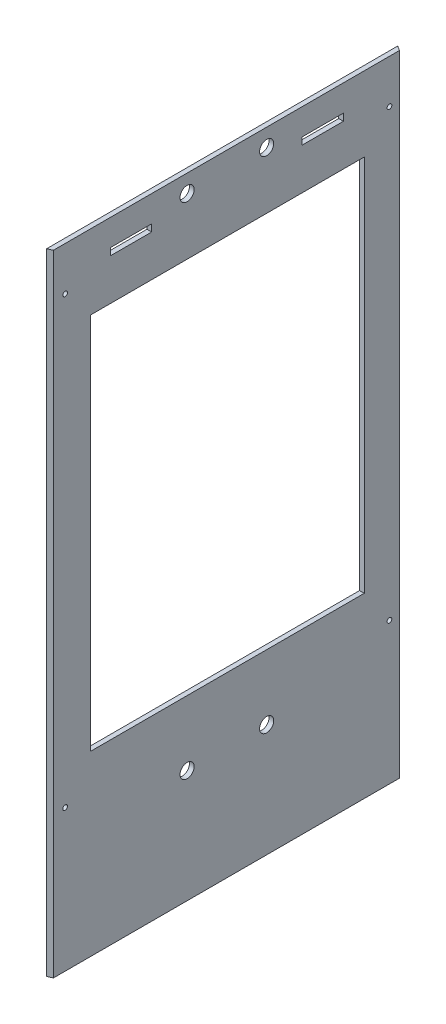
SolidWorks part; units mm, degrees
ref_plane "Спереди" through (0, 0, 0) normal (0, 0, 1) x (1, 0, 0)
ref_plane "Сверху" through (0, 0, 0) normal (0, 1, 0) x (1, 0, 0)
ref_plane "Справа" through (0, 0, 0) normal (1, 0, 0) x (0, 0, -1)
sketch "Эскиз1" plane through (0, 0, 0) normal (0, 1, 0) x (1, 0, 0)
  line L0 (4.0186, 1.7475) -> (79.181, -66.868) construction
  line L1 (0, 0) -> (4, 1.7645)
  line L2 (0, 0) -> (0, 297.3876)
  line L3 (0, 297.3876) -> (4, 294.8273)
  line L4 (4, 1.7645) -> (4, 294.8273)
  dimension "D1" = 4
extrude "Вытянуть1" add sketch "Эскиз1" along normal up to surface (533.7137 mm away)
sketch "Эскиз2" plane through (0, 0, 0) normal (-1, 0, 0) x (0, 0, 1)
  line L0 (-272.3275, 260.902) -> (-272.3275, -22.3628)
  line L1 (-272.3275, 260.902) -> (-25.1909, 260.902)
  line L3 (-272.3275, -22.3628) -> (-25.1909, -22.3628)
  line L4 (-25.1909, 260.902) -> (-25.1909, -22.3628)
  line L6 (-264.3275, 152.3571) -> (-192.5685, 152.3571) construction
sketch "Sketch1" plane through (0, 0, 0) normal (-1, 0, 0) x (0, 0, 1)
  line L0 (-149.0559, 533.7137) -> (-149.0559, 365.9424) construction
  line L2 (-466.2387, 150.5) -> (190.429, 150.5) construction
  line L3 (-297.6324, 0.5) -> (0.0403, 0.5) construction
  line L4 (-507.1548, 470.5) -> (192.6943, 470.5) construction
  line L5 (-451.9035, 310.5) -> (226.1799, 310.5) construction
  line L7 (-33.0559, 150.5) -> (-265.0559, 150.5)
  line L8 (-33.0559, 150.5) -> (-33.0559, 470.5)
  line L9 (-33.0559, 470.5) -> (-265.0559, 470.5)
  line L10 (-265.0559, 150.5) -> (-265.0559, 470.5)
  line L11 (-33.0559, 150.5) -> (-265.0559, 470.5) construction
  line L12 (-33.0559, 470.5) -> (-265.0559, 150.5) construction
  point P9 (-149.0559, 310.5)
  dimension "D1" = 150
  dimension "D2" = 320
  dimension "D3" = 160
extrude "Cut-Extrude1" cut sketch "Sketch1" against normal through all
sketch "Sketch2" plane through (0, 0, 0) normal (-1, 0, 0) x (0, 0, 1)
  line L0 (-325.7416, 505.5) -> (32.5763, 505.5) construction
  line L1 (-33.0559, 470.5) -> (-265.0559, 470.5) construction
  line L2 (-247.3876, 583.7888) -> (-247.3876, 553.0639) construction
  line L4 (-297.3876, 533.7137) -> (-297.3876, 0) construction
  line L5 (-148.6938, 533.7137) -> (-148.6938, 623.8727) construction
  line L6 (-247.3876, 505.5) -> (-212.3876, 505.5)
  line L7 (-247.3876, 505.5) -> (-247.3876, 511.5)
  line L8 (-247.3876, 511.5) -> (-212.3876, 511.5)
  line L9 (-212.3876, 505.5) -> (-212.3876, 511.5)
  line L11 (-50, 505.5) -> (-50, 511.5)
  line L12 (-50, 505.5) -> (-85, 505.5)
  line L13 (-85, 505.5) -> (-85, 511.5)
  line L14 (-50, 511.5) -> (-85, 511.5)
  dimension "D1" = 35
  dimension "D2" = 50
extrude "Cut-Extrude2" cut sketch "Sketch2" against normal through all
sketch "Sketch3" plane through (0, 0, 0) normal (-1, 0, 0) x (0, 0, 1)
  line L0 (-297.3876, 533.7137) -> (-297.3876, 0) construction
  line L1 (-297.3876, 533.7137) -> (0, 533.7137) construction
  line L2 (0, 533.7137) -> (0, 0) construction
  line L3 (-296.494, 533.7137) -> (-0.2197, 533.7137) construction
  line L4 (-297.6324, 0.5) -> (0.0403, 0.5) construction
  circle A0 centre (-182.3876, 518.7137) radius 6
  circle A1 centre (-115, 518.7137) radius 6
  circle A2 centre (-182.3876, 95.5) radius 6
  circle A3 centre (-115, 95.5) radius 6
  dimension "D1" = 115
  dimension "D3" = 115
  dimension "D5" = 95
  dimension "D7" = 115
  dimension "D2" = 15
  dimension "D4" = 15
  dimension "D6" = 115
extrude "Cut-Extrude3" cut sketch "Sketch3" against normal through all
sketch "Sketch4" plane through (0, 0, 0) normal (-1, 0, 0) x (0, 0, 1)
  line L0 (-296.494, 533.7137) -> (-0.2197, 533.7137) construction
  line L1 (-297.3876, 533.7137) -> (-297.3876, 0) construction
  line L2 (-149.0559, 533.7137) -> (-149.0559, 576.7744) construction
  line L3 (-297.3876, 0) -> (0, 0) construction
  circle A0 centre (-286.3876, 496.7137) radius 2
  circle A1 centre (-11.7242, 496.7137) radius 2
  circle A2 centre (-286.3876, 120) radius 2
  circle A3 centre (-11.7242, 120) radius 2
  dimension "D1" = 37
  dimension "D3" = 120
  dimension "D2" = 11
  dimension "D4" = 11
extrude "Cut-Extrude4" cut sketch "Sketch4" against normal through all
